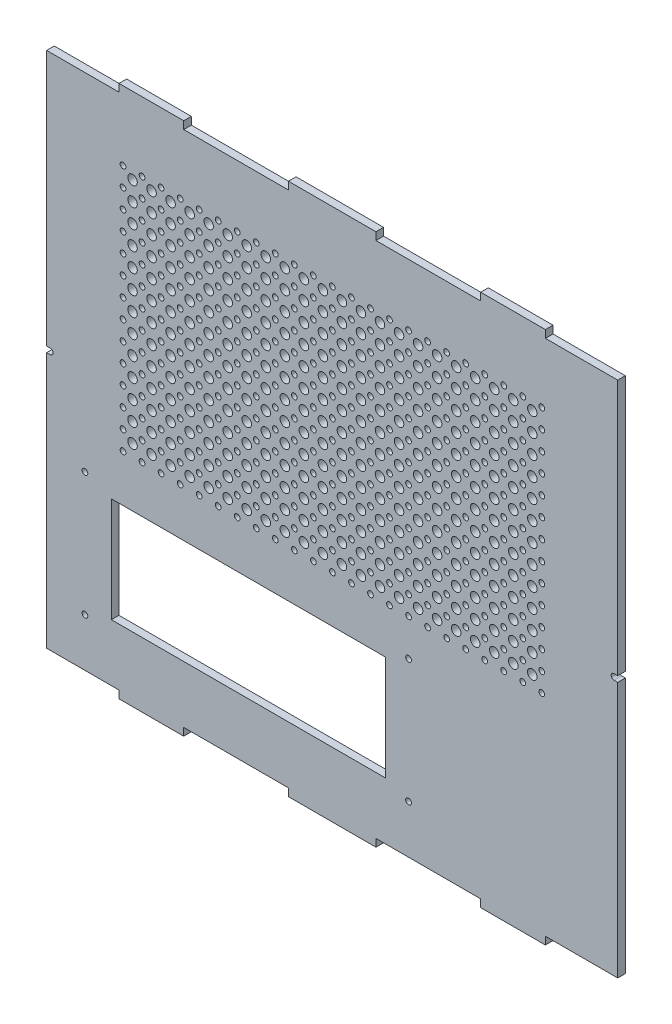
SolidWorks part; units mm, degrees
ref_plane "Front" through (0, 0, 0) normal (0, 0, 1) x (1, 0, 0)
ref_plane "Top" through (0, 0, 0) normal (0, 1, 0) x (1, 0, 0)
ref_plane "Right" through (0, 0, 0) normal (1, 0, 0) x (0, 0, -1)
sketch "Sketch1" plane through (0, 0, 0) normal (0, 0, 1) x (1, 0, 0)
  line L0 (-112, 140) -> (-112, 136)
  line L1 (150, -140) -> (-150, -140)
  line L2 (150, -140) -> (150, 140)
  line L3 (150, 140) -> (-150, 140)
  line L4 (-150, -140) -> (-150, -1.5)
  line L5 (150, -140) -> (-150, 140) construction
  line L6 (150, 140) -> (-150, -140) construction
  line L7 (-78, 136) -> (-78, 140)
  line L8 (-78, 140) -> (-112, 140)
  line L9 (-23, 136) -> (-23, 140)
  line L10 (-23, 140) -> (23, 140)
  line L11 (23, 136) -> (23, 140)
  line L12 (78, 140) -> (112, 140)
  line L13 (78, 136) -> (78, 140)
  line L14 (112, 140) -> (112, 136)
  line L15 (112, 136) -> (-112, 136) construction
  line L16 (-112, 136) -> (112, 136)
  line L17 (-150, 0) -> (150, 0) construction
  line L18 (-112, -136) -> (112, -136)
  line L19 (-78, -140) -> (-112, -140)
  line L20 (-78, -136) -> (-78, -140)
  line L21 (-112, -140) -> (-112, -136)
  line L22 (112, -140) -> (112, -136)
  line L23 (78, -136) -> (78, -140)
  line L24 (78, -140) -> (112, -140)
  line L25 (23, -136) -> (23, -140)
  line L26 (-23, -140) -> (23, -140)
  line L27 (-23, -136) -> (-23, -140)
  line L28 (-150, 136) -> (150, 136)
  line L29 (112, -136) -> (150, -136)
  line L30 (-112, -136) -> (-150, -136)
  line L31 (-150, 0) -> (-148.0495, 0) construction
  line L32 (-150, 1.5) -> (-148.0495, 1.5)
  line L33 (-150, -1.5) -> (-148.0495, -1.5)
  line L34 (-150, 1.5) -> (-150, 140)
  line L35 (0, 0) -> (0, -136) construction
  line L36 (150, 0) -> (148.0495, 0) construction
  line L37 (150, -1.5) -> (148.0495, -1.5)
  line L38 (150, 1.5) -> (148.0495, 1.5)
  line L39 (116.6123, 108.6823) -> (-116.3877, 108.6823) construction
  line L40 (116.6123, 108.6823) -> (116.6123, -35.3177) construction
  line L41 (116.6123, -35.3177) -> (-116.3877, -35.3177) construction
  line L42 (-116.3877, 108.6823) -> (-116.3877, -35.3177) construction
  line L43 (116.6123, 108.6823) -> (-116.3877, -35.3177) construction
  line L44 (116.6123, -35.3177) -> (-116.3877, 108.6823) construction
  line L46 (28, -106) -> (-116, -106)
  line L47 (28, -106) -> (28, -51)
  line L48 (28, -51) -> (-116, -51)
  line L49 (-116, -106) -> (-116, -51)
  line L50 (28, -106) -> (-116, -51) construction
  line L51 (28, -51) -> (-116, -106) construction
  line L52 (-129.8891, -45.6951) -> (40.1123, -45.6951) construction
  line L53 (-129.8891, -45.6951) -> (-129.8891, -110.6262) construction
  line L54 (-129.8891, -110.6262) -> (40.1123, -110.6262) construction
  line L55 (40.1123, -45.6951) -> (40.1123, -110.6262) construction
  line L56 (-44.8884, -110.6262) -> (-44.8884, -45.6951) construction
  line L57 (-129.8891, -78.1607) -> (40.1123, -78.1607) construction
  arc A0 (148.0495, -1.5) -> (148.0495, 1.5) centre (148.0495, 0) cw
  arc A1 (-148.0495, -1.5) -> (-148.0495, 1.5) centre (-148.0495, 0) ccw
  circle A2 centre (-129.8891, -45.6951) radius 1.5
  circle A3 centre (40.1123, -45.6951) radius 1.5
  circle A4 centre (-109.8877, 103.6823) radius 1.5
  circle A5 centre (-99.8877, 103.6823) radius 1.5
  circle A6 centre (-89.8877, 103.6823) radius 1.5
  circle A7 centre (-79.8877, 103.6823) radius 1.5
  circle A8 centre (-69.8877, 103.6823) radius 1.5
  circle A9 centre (-59.8877, 103.6823) radius 1.5
  circle A10 centre (-49.8877, 103.6823) radius 1.5
  circle A11 centre (-39.8877, 103.6823) radius 1.5
  circle A12 centre (-29.8877, 103.6823) radius 1.5
  circle A13 centre (-19.8877, 103.6823) radius 1.5
  circle A14 centre (-9.8877, 103.6823) radius 1.5
  circle A15 centre (0.1123, 103.6823) radius 1.5
  circle A16 centre (10.1123, 103.6823) radius 1.5
  circle A17 centre (20.1123, 103.6823) radius 1.5
  circle A18 centre (30.1123, 103.6823) radius 1.5
  circle A19 centre (40.1123, 103.6823) radius 1.5
  circle A20 centre (50.1123, 103.6823) radius 1.5
  circle A21 centre (60.1123, 103.6823) radius 1.5
  circle A22 centre (70.1123, 103.6823) radius 1.5
  circle A23 centre (80.1123, 103.6823) radius 1.5
  circle A24 centre (90.1123, 103.6823) radius 1.5
  circle A25 centre (100.1123, 103.6823) radius 1.5
  circle A26 centre (110.1123, 103.6823) radius 1.5
  circle A27 centre (-99.8877, 93.6823) radius 1.5
  circle A28 centre (-89.8877, 93.6823) radius 1.5
  circle A29 centre (-79.8877, 93.6823) radius 1.5
  circle A30 centre (-69.8877, 93.6823) radius 1.5
  circle A31 centre (-59.8877, 93.6823) radius 1.5
  circle A32 centre (-49.8877, 93.6823) radius 1.5
  circle A33 centre (-39.8877, 93.6823) radius 1.5
  circle A34 centre (-29.8877, 93.6823) radius 1.5
  circle A35 centre (-19.8877, 93.6823) radius 1.5
  circle A36 centre (-9.8877, 93.6823) radius 1.5
  circle A37 centre (0.1123, 93.6823) radius 1.5
  circle A38 centre (10.1123, 93.6823) radius 1.5
  circle A39 centre (20.1123, 93.6823) radius 1.5
  circle A40 centre (30.1123, 93.6823) radius 1.5
  circle A41 centre (40.1123, 93.6823) radius 1.5
  circle A42 centre (50.1123, 93.6823) radius 1.5
  circle A43 centre (60.1123, 93.6823) radius 1.5
  circle A44 centre (70.1123, 93.6823) radius 1.5
  circle A45 centre (80.1123, 93.6823) radius 1.5
  circle A46 centre (90.1123, 93.6823) radius 1.5
  circle A47 centre (100.1123, 93.6823) radius 1.5
  circle A48 centre (110.1123, 93.6823) radius 1.5
  circle A49 centre (-99.8877, 83.6823) radius 1.5
  circle A50 centre (-89.8877, 83.6823) radius 1.5
  circle A51 centre (-79.8877, 83.6823) radius 1.5
  circle A52 centre (-69.8877, 83.6823) radius 1.5
  circle A53 centre (-59.8877, 83.6823) radius 1.5
  circle A54 centre (-49.8877, 83.6823) radius 1.5
  circle A55 centre (-39.8877, 83.6823) radius 1.5
  circle A56 centre (-29.8877, 83.6823) radius 1.5
  circle A57 centre (-19.8877, 83.6823) radius 1.5
  circle A58 centre (-9.8877, 83.6823) radius 1.5
  circle A59 centre (0.1123, 83.6823) radius 1.5
  circle A60 centre (10.1123, 83.6823) radius 1.5
  circle A61 centre (20.1123, 83.6823) radius 1.5
  circle A62 centre (30.1123, 83.6823) radius 1.5
  circle A63 centre (40.1123, 83.6823) radius 1.5
  circle A64 centre (50.1123, 83.6823) radius 1.5
  circle A65 centre (60.1123, 83.6823) radius 1.5
  circle A66 centre (70.1123, 83.6823) radius 1.5
  circle A67 centre (80.1123, 83.6823) radius 1.5
  circle A68 centre (90.1123, 83.6823) radius 1.5
  circle A69 centre (100.1123, 83.6823) radius 1.5
  circle A70 centre (110.1123, 83.6823) radius 1.5
  circle A71 centre (-99.8877, 73.6823) radius 1.5
  circle A72 centre (-89.8877, 73.6823) radius 1.5
  circle A73 centre (-79.8877, 73.6823) radius 1.5
  circle A74 centre (-69.8877, 73.6823) radius 1.5
  circle A75 centre (-59.8877, 73.6823) radius 1.5
  circle A76 centre (-49.8877, 73.6823) radius 1.5
  circle A77 centre (-39.8877, 73.6823) radius 1.5
  circle A78 centre (-29.8877, 73.6823) radius 1.5
  circle A79 centre (-19.8877, 73.6823) radius 1.5
  circle A80 centre (-9.8877, 73.6823) radius 1.5
  circle A81 centre (0.1123, 73.6823) radius 1.5
  circle A82 centre (10.1123, 73.6823) radius 1.5
  circle A83 centre (20.1123, 73.6823) radius 1.5
  circle A84 centre (30.1123, 73.6823) radius 1.5
  circle A85 centre (40.1123, 73.6823) radius 1.5
  circle A86 centre (50.1123, 73.6823) radius 1.5
  circle A87 centre (60.1123, 73.6823) radius 1.5
  circle A88 centre (70.1123, 73.6823) radius 1.5
  circle A89 centre (80.1123, 73.6823) radius 1.5
  circle A90 centre (90.1123, 73.6823) radius 1.5
  circle A91 centre (100.1123, 73.6823) radius 1.5
  circle A92 centre (110.1123, 73.6823) radius 1.5
  circle A93 centre (-99.8877, 63.6823) radius 1.5
  circle A94 centre (-89.8877, 63.6823) radius 1.5
  circle A95 centre (-79.8877, 63.6823) radius 1.5
  circle A96 centre (-69.8877, 63.6823) radius 1.5
  circle A97 centre (-59.8877, 63.6823) radius 1.5
  circle A98 centre (-49.8877, 63.6823) radius 1.5
  circle A99 centre (-39.8877, 63.6823) radius 1.5
  circle A100 centre (-29.8877, 63.6823) radius 1.5
  circle A101 centre (-19.8877, 63.6823) radius 1.5
  circle A102 centre (-9.8877, 63.6823) radius 1.5
  circle A103 centre (0.1123, 63.6823) radius 1.5
  circle A104 centre (10.1123, 63.6823) radius 1.5
  circle A105 centre (20.1123, 63.6823) radius 1.5
  circle A106 centre (30.1123, 63.6823) radius 1.5
  circle A107 centre (40.1123, 63.6823) radius 1.5
  circle A108 centre (50.1123, 63.6823) radius 1.5
  circle A109 centre (60.1123, 63.6823) radius 1.5
  circle A110 centre (70.1123, 63.6823) radius 1.5
  circle A111 centre (80.1123, 63.6823) radius 1.5
  circle A112 centre (90.1123, 63.6823) radius 1.5
  circle A113 centre (100.1123, 63.6823) radius 1.5
  circle A114 centre (110.1123, 63.6823) radius 1.5
  circle A115 centre (-99.8877, 53.6823) radius 1.5
  circle A116 centre (-89.8877, 53.6823) radius 1.5
  circle A117 centre (-79.8877, 53.6823) radius 1.5
  circle A118 centre (-69.8877, 53.6823) radius 1.5
  circle A119 centre (-59.8877, 53.6823) radius 1.5
  circle A120 centre (-49.8877, 53.6823) radius 1.5
  circle A121 centre (-39.8877, 53.6823) radius 1.5
  circle A122 centre (-29.8877, 53.6823) radius 1.5
  circle A123 centre (-19.8877, 53.6823) radius 1.5
  circle A124 centre (-9.8877, 53.6823) radius 1.5
  circle A125 centre (0.1123, 53.6823) radius 1.5
  circle A126 centre (10.1123, 53.6823) radius 1.5
  circle A127 centre (20.1123, 53.6823) radius 1.5
  circle A128 centre (30.1123, 53.6823) radius 1.5
  circle A129 centre (40.1123, 53.6823) radius 1.5
  circle A130 centre (50.1123, 53.6823) radius 1.5
  circle A131 centre (60.1123, 53.6823) radius 1.5
  circle A132 centre (70.1123, 53.6823) radius 1.5
  circle A133 centre (80.1123, 53.6823) radius 1.5
  circle A134 centre (90.1123, 53.6823) radius 1.5
  circle A135 centre (100.1123, 53.6823) radius 1.5
  circle A136 centre (110.1123, 53.6823) radius 1.5
  circle A137 centre (-99.8877, 43.6823) radius 1.5
  circle A138 centre (-89.8877, 43.6823) radius 1.5
  circle A139 centre (-79.8877, 43.6823) radius 1.5
  circle A140 centre (-69.8877, 43.6823) radius 1.5
  circle A141 centre (-59.8877, 43.6823) radius 1.5
  circle A142 centre (-49.8877, 43.6823) radius 1.5
  circle A143 centre (-39.8877, 43.6823) radius 1.5
  circle A144 centre (-29.8877, 43.6823) radius 1.5
  circle A145 centre (-19.8877, 43.6823) radius 1.5
  circle A146 centre (-9.8877, 43.6823) radius 1.5
  circle A147 centre (0.1123, 43.6823) radius 1.5
  circle A148 centre (10.1123, 43.6823) radius 1.5
  circle A149 centre (20.1123, 43.6823) radius 1.5
  circle A150 centre (30.1123, 43.6823) radius 1.5
  circle A151 centre (40.1123, 43.6823) radius 1.5
  circle A152 centre (50.1123, 43.6823) radius 1.5
  circle A153 centre (60.1123, 43.6823) radius 1.5
  circle A154 centre (70.1123, 43.6823) radius 1.5
  circle A155 centre (80.1123, 43.6823) radius 1.5
  circle A156 centre (90.1123, 43.6823) radius 1.5
  circle A157 centre (100.1123, 43.6823) radius 1.5
  circle A158 centre (110.1123, 43.6823) radius 1.5
  circle A159 centre (-99.8877, 33.6823) radius 1.5
  circle A160 centre (-89.8877, 33.6823) radius 1.5
  circle A161 centre (-79.8877, 33.6823) radius 1.5
  circle A162 centre (-69.8877, 33.6823) radius 1.5
  circle A163 centre (-59.8877, 33.6823) radius 1.5
  circle A164 centre (-49.8877, 33.6823) radius 1.5
  circle A165 centre (-39.8877, 33.6823) radius 1.5
  circle A166 centre (-29.8877, 33.6823) radius 1.5
  circle A167 centre (-19.8877, 33.6823) radius 1.5
  circle A168 centre (-9.8877, 33.6823) radius 1.5
  circle A169 centre (0.1123, 33.6823) radius 1.5
  circle A170 centre (10.1123, 33.6823) radius 1.5
  circle A171 centre (20.1123, 33.6823) radius 1.5
  circle A172 centre (30.1123, 33.6823) radius 1.5
  circle A173 centre (40.1123, 33.6823) radius 1.5
  circle A174 centre (50.1123, 33.6823) radius 1.5
  circle A175 centre (60.1123, 33.6823) radius 1.5
  circle A176 centre (70.1123, 33.6823) radius 1.5
  circle A177 centre (80.1123, 33.6823) radius 1.5
  circle A178 centre (90.1123, 33.6823) radius 1.5
  circle A179 centre (100.1123, 33.6823) radius 1.5
  circle A180 centre (110.1123, 33.6823) radius 1.5
  circle A181 centre (-99.8877, 23.6823) radius 1.5
  circle A182 centre (-89.8877, 23.6823) radius 1.5
  circle A183 centre (-79.8877, 23.6823) radius 1.5
  circle A184 centre (-69.8877, 23.6823) radius 1.5
  circle A185 centre (-59.8877, 23.6823) radius 1.5
  circle A186 centre (-49.8877, 23.6823) radius 1.5
  circle A187 centre (-39.8877, 23.6823) radius 1.5
  circle A188 centre (-29.8877, 23.6823) radius 1.5
  circle A189 centre (-19.8877, 23.6823) radius 1.5
  circle A190 centre (-9.8877, 23.6823) radius 1.5
  circle A191 centre (0.1123, 23.6823) radius 1.5
  circle A192 centre (10.1123, 23.6823) radius 1.5
  circle A193 centre (20.1123, 23.6823) radius 1.5
  circle A194 centre (30.1123, 23.6823) radius 1.5
  circle A195 centre (40.1123, 23.6823) radius 1.5
  circle A196 centre (50.1123, 23.6823) radius 1.5
  circle A197 centre (60.1123, 23.6823) radius 1.5
  circle A198 centre (70.1123, 23.6823) radius 1.5
  circle A199 centre (80.1123, 23.6823) radius 1.5
  circle A200 centre (90.1123, 23.6823) radius 1.5
  circle A201 centre (100.1123, 23.6823) radius 1.5
  circle A202 centre (110.1123, 23.6823) radius 1.5
  circle A203 centre (-99.8877, 13.6823) radius 1.5
  circle A204 centre (-89.8877, 13.6823) radius 1.5
  circle A205 centre (-79.8877, 13.6823) radius 1.5
  circle A206 centre (-69.8877, 13.6823) radius 1.5
  circle A207 centre (-59.8877, 13.6823) radius 1.5
  circle A208 centre (-49.8877, 13.6823) radius 1.5
  circle A209 centre (-39.8877, 13.6823) radius 1.5
  circle A210 centre (-29.8877, 13.6823) radius 1.5
  circle A211 centre (-19.8877, 13.6823) radius 1.5
  circle A212 centre (-9.8877, 13.6823) radius 1.5
  circle A213 centre (0.1123, 13.6823) radius 1.5
  circle A214 centre (10.1123, 13.6823) radius 1.5
  circle A215 centre (20.1123, 13.6823) radius 1.5
  circle A216 centre (30.1123, 13.6823) radius 1.5
  circle A217 centre (40.1123, 13.6823) radius 1.5
  circle A218 centre (50.1123, 13.6823) radius 1.5
  circle A219 centre (60.1123, 13.6823) radius 1.5
  circle A220 centre (70.1123, 13.6823) radius 1.5
  circle A221 centre (80.1123, 13.6823) radius 1.5
  circle A222 centre (90.1123, 13.6823) radius 1.5
  circle A223 centre (100.1123, 13.6823) radius 1.5
  circle A224 centre (110.1123, 13.6823) radius 1.5
  circle A225 centre (-99.8877, 3.6823) radius 1.5
  circle A226 centre (-89.8877, 3.6823) radius 1.5
  circle A227 centre (-79.8877, 3.6823) radius 1.5
  circle A228 centre (-69.8877, 3.6823) radius 1.5
  circle A229 centre (-59.8877, 3.6823) radius 1.5
  circle A230 centre (-49.8877, 3.6823) radius 1.5
  circle A231 centre (-39.8877, 3.6823) radius 1.5
  circle A232 centre (-29.8877, 3.6823) radius 1.5
  circle A233 centre (-19.8877, 3.6823) radius 1.5
  circle A234 centre (-9.8877, 3.6823) radius 1.5
  circle A235 centre (0.1123, 3.6823) radius 1.5
  circle A236 centre (10.1123, 3.6823) radius 1.5
  circle A237 centre (20.1123, 3.6823) radius 1.5
  circle A238 centre (30.1123, 3.6823) radius 1.5
  circle A239 centre (40.1123, 3.6823) radius 1.5
  circle A240 centre (50.1123, 3.6823) radius 1.5
  circle A241 centre (60.1123, 3.6823) radius 1.5
  circle A242 centre (70.1123, 3.6823) radius 1.5
  circle A243 centre (80.1123, 3.6823) radius 1.5
  circle A244 centre (90.1123, 3.6823) radius 1.5
  circle A245 centre (100.1123, 3.6823) radius 1.5
  circle A246 centre (110.1123, 3.6823) radius 1.5
  circle A247 centre (-99.8877, -6.3177) radius 1.5
  circle A248 centre (-89.8877, -6.3177) radius 1.5
  circle A249 centre (-79.8877, -6.3177) radius 1.5
  circle A250 centre (-69.8877, -6.3177) radius 1.5
  circle A251 centre (-59.8877, -6.3177) radius 1.5
  circle A252 centre (-49.8877, -6.3177) radius 1.5
  circle A253 centre (-39.8877, -6.3177) radius 1.5
  circle A254 centre (-29.8877, -6.3177) radius 1.5
  circle A255 centre (-19.8877, -6.3177) radius 1.5
  circle A256 centre (-9.8877, -6.3177) radius 1.5
  circle A257 centre (0.1123, -6.3177) radius 1.5
  circle A258 centre (10.1123, -6.3177) radius 1.5
  circle A259 centre (20.1123, -6.3177) radius 1.5
  circle A260 centre (30.1123, -6.3177) radius 1.5
  circle A261 centre (40.1123, -6.3177) radius 1.5
  circle A262 centre (50.1123, -6.3177) radius 1.5
  circle A263 centre (60.1123, -6.3177) radius 1.5
  circle A264 centre (70.1123, -6.3177) radius 1.5
  circle A265 centre (80.1123, -6.3177) radius 1.5
  circle A266 centre (90.1123, -6.3177) radius 1.5
  circle A267 centre (100.1123, -6.3177) radius 1.5
  circle A268 centre (110.1123, -6.3177) radius 1.5
  circle A269 centre (-99.8877, -16.3177) radius 1.5
  circle A270 centre (-89.8877, -16.3177) radius 1.5
  circle A271 centre (-79.8877, -16.3177) radius 1.5
  circle A272 centre (-69.8877, -16.3177) radius 1.5
  circle A273 centre (-59.8877, -16.3177) radius 1.5
  circle A274 centre (-49.8877, -16.3177) radius 1.5
  circle A275 centre (-39.8877, -16.3177) radius 1.5
  circle A276 centre (-29.8877, -16.3177) radius 1.5
  circle A277 centre (-19.8877, -16.3177) radius 1.5
  circle A278 centre (-9.8877, -16.3177) radius 1.5
  circle A279 centre (0.1123, -16.3177) radius 1.5
  circle A280 centre (10.1123, -16.3177) radius 1.5
  circle A281 centre (20.1123, -16.3177) radius 1.5
  circle A282 centre (30.1123, -16.3177) radius 1.5
  circle A283 centre (40.1123, -16.3177) radius 1.5
  circle A284 centre (50.1123, -16.3177) radius 1.5
  circle A285 centre (60.1123, -16.3177) radius 1.5
  circle A286 centre (70.1123, -16.3177) radius 1.5
  circle A287 centre (80.1123, -16.3177) radius 1.5
  circle A288 centre (90.1123, -16.3177) radius 1.5
  circle A289 centre (100.1123, -16.3177) radius 1.5
  circle A290 centre (110.1123, -16.3177) radius 1.5
  circle A291 centre (-99.8877, -26.3177) radius 1.5
  circle A292 centre (-89.8877, -26.3177) radius 1.5
  circle A293 centre (-79.8877, -26.3177) radius 1.5
  circle A294 centre (-69.8877, -26.3177) radius 1.5
  circle A295 centre (-59.8877, -26.3177) radius 1.5
  circle A296 centre (-49.8877, -26.3177) radius 1.5
  circle A297 centre (-39.8877, -26.3177) radius 1.5
  circle A298 centre (-29.8877, -26.3177) radius 1.5
  circle A299 centre (-19.8877, -26.3177) radius 1.5
  circle A300 centre (-9.8877, -26.3177) radius 1.5
  circle A301 centre (0.1123, -26.3177) radius 1.5
  circle A302 centre (10.1123, -26.3177) radius 1.5
  circle A303 centre (20.1123, -26.3177) radius 1.5
  circle A304 centre (30.1123, -26.3177) radius 1.5
  circle A305 centre (40.1123, -26.3177) radius 1.5
  circle A306 centre (50.1123, -26.3177) radius 1.5
  circle A307 centre (60.1123, -26.3177) radius 1.5
  circle A308 centre (70.1123, -26.3177) radius 1.5
  circle A309 centre (80.1123, -26.3177) radius 1.5
  circle A310 centre (90.1123, -26.3177) radius 1.5
  circle A311 centre (100.1123, -26.3177) radius 1.5
  circle A312 centre (110.1123, -26.3177) radius 1.5
  circle A313 centre (-109.8877, 93.6823) radius 1.5
  circle A314 centre (-109.8877, 83.6823) radius 1.5
  circle A315 centre (-109.8877, 73.6823) radius 1.5
  circle A316 centre (-109.8877, 63.6823) radius 1.5
  circle A317 centre (-109.8877, 53.6823) radius 1.5
  circle A318 centre (-109.8877, 43.6823) radius 1.5
  circle A319 centre (-109.8877, 33.6823) radius 1.5
  circle A320 centre (-109.8877, 23.6823) radius 1.5
  circle A321 centre (-109.8877, 13.6823) radius 1.5
  circle A322 centre (-109.8877, 3.6823) radius 1.5
  circle A323 centre (-109.8877, -6.3177) radius 1.5
  circle A324 centre (-109.8877, -16.3177) radius 1.5
  circle A325 centre (-109.8877, -26.3177) radius 1.5
  circle A326 centre (-94.8877, 99.6823) radius 2.5
  circle A327 centre (-84.8877, 99.6823) radius 2.5
  circle A328 centre (-74.8877, 99.6823) radius 2.5
  circle A329 centre (-64.8877, 99.6823) radius 2.5
  circle A330 centre (-54.8877, 99.6823) radius 2.5
  circle A331 centre (-44.8877, 99.6823) radius 2.5
  circle A332 centre (-34.8877, 99.6823) radius 2.5
  circle A333 centre (-24.8877, 99.6823) radius 2.5
  circle A334 centre (-14.8877, 99.6823) radius 2.5
  circle A335 centre (-4.8877, 99.6823) radius 2.5
  circle A336 centre (5.1123, 99.6823) radius 2.5
  circle A337 centre (15.1123, 99.6823) radius 2.5
  circle A338 centre (25.1123, 99.6823) radius 2.5
  circle A339 centre (35.1123, 99.6823) radius 2.5
  circle A340 centre (45.1123, 99.6823) radius 2.5
  circle A341 centre (55.1123, 99.6823) radius 2.5
  circle A342 centre (65.1123, 99.6823) radius 2.5
  circle A343 centre (75.1123, 99.6823) radius 2.5
  circle A344 centre (85.1123, 99.6823) radius 2.5
  circle A345 centre (95.1123, 99.6823) radius 2.5
  circle A346 centre (105.1123, 99.6823) radius 2.5
  circle A347 centre (-94.8877, 89.6823) radius 2.5
  circle A348 centre (-84.8877, 89.6823) radius 2.5
  circle A349 centre (-74.8877, 89.6823) radius 2.5
  circle A350 centre (-64.8877, 89.6823) radius 2.5
  circle A351 centre (-54.8877, 89.6823) radius 2.5
  circle A352 centre (-44.8877, 89.6823) radius 2.5
  circle A353 centre (-34.8877, 89.6823) radius 2.5
  circle A354 centre (-24.8877, 89.6823) radius 2.5
  circle A355 centre (-14.8877, 89.6823) radius 2.5
  circle A356 centre (-4.8877, 89.6823) radius 2.5
  circle A357 centre (5.1123, 89.6823) radius 2.5
  circle A358 centre (15.1123, 89.6823) radius 2.5
  circle A359 centre (25.1123, 89.6823) radius 2.5
  circle A360 centre (35.1123, 89.6823) radius 2.5
  circle A361 centre (45.1123, 89.6823) radius 2.5
  circle A362 centre (55.1123, 89.6823) radius 2.5
  circle A363 centre (65.1123, 89.6823) radius 2.5
  circle A364 centre (75.1123, 89.6823) radius 2.5
  circle A365 centre (85.1123, 89.6823) radius 2.5
  circle A366 centre (95.1123, 89.6823) radius 2.5
  circle A367 centre (105.1123, 89.6823) radius 2.5
  circle A368 centre (-94.8877, 79.6823) radius 2.5
  circle A369 centre (-84.8877, 79.6823) radius 2.5
  circle A370 centre (-74.8877, 79.6823) radius 2.5
  circle A371 centre (-64.8877, 79.6823) radius 2.5
  circle A372 centre (-54.8877, 79.6823) radius 2.5
  circle A373 centre (-44.8877, 79.6823) radius 2.5
  circle A374 centre (-34.8877, 79.6823) radius 2.5
  circle A375 centre (-24.8877, 79.6823) radius 2.5
  circle A376 centre (-14.8877, 79.6823) radius 2.5
  circle A377 centre (-4.8877, 79.6823) radius 2.5
  circle A378 centre (5.1123, 79.6823) radius 2.5
  circle A379 centre (15.1123, 79.6823) radius 2.5
  circle A380 centre (25.1123, 79.6823) radius 2.5
  circle A381 centre (35.1123, 79.6823) radius 2.5
  circle A382 centre (45.1123, 79.6823) radius 2.5
  circle A383 centre (55.1123, 79.6823) radius 2.5
  circle A384 centre (65.1123, 79.6823) radius 2.5
  circle A385 centre (75.1123, 79.6823) radius 2.5
  circle A386 centre (85.1123, 79.6823) radius 2.5
  circle A387 centre (95.1123, 79.6823) radius 2.5
  circle A388 centre (105.1123, 79.6823) radius 2.5
  circle A389 centre (-94.8877, 69.6823) radius 2.5
  circle A390 centre (-84.8877, 69.6823) radius 2.5
  circle A391 centre (-74.8877, 69.6823) radius 2.5
  circle A392 centre (-64.8877, 69.6823) radius 2.5
  circle A393 centre (-54.8877, 69.6823) radius 2.5
  circle A394 centre (-44.8877, 69.6823) radius 2.5
  circle A395 centre (-34.8877, 69.6823) radius 2.5
  circle A396 centre (-24.8877, 69.6823) radius 2.5
  circle A397 centre (-14.8877, 69.6823) radius 2.5
  circle A398 centre (-4.8877, 69.6823) radius 2.5
  circle A399 centre (5.1123, 69.6823) radius 2.5
  circle A400 centre (15.1123, 69.6823) radius 2.5
  circle A401 centre (25.1123, 69.6823) radius 2.5
  circle A402 centre (35.1123, 69.6823) radius 2.5
  circle A403 centre (45.1123, 69.6823) radius 2.5
  circle A404 centre (55.1123, 69.6823) radius 2.5
  circle A405 centre (65.1123, 69.6823) radius 2.5
  circle A406 centre (75.1123, 69.6823) radius 2.5
  circle A407 centre (85.1123, 69.6823) radius 2.5
  circle A408 centre (95.1123, 69.6823) radius 2.5
  circle A409 centre (105.1123, 69.6823) radius 2.5
  circle A410 centre (-94.8877, 59.6823) radius 2.5
  circle A411 centre (-84.8877, 59.6823) radius 2.5
  circle A412 centre (-74.8877, 59.6823) radius 2.5
  circle A413 centre (-64.8877, 59.6823) radius 2.5
  circle A414 centre (-54.8877, 59.6823) radius 2.5
  circle A415 centre (-44.8877, 59.6823) radius 2.5
  circle A416 centre (-34.8877, 59.6823) radius 2.5
  circle A417 centre (-24.8877, 59.6823) radius 2.5
  circle A418 centre (-104.8877, 99.6823) radius 2.5
  circle A419 centre (-14.8877, 59.6823) radius 2.5
  circle A420 centre (-4.8877, 59.6823) radius 2.5
  circle A421 centre (5.1123, 59.6823) radius 2.5
  circle A422 centre (15.1123, 59.6823) radius 2.5
  circle A423 centre (25.1123, 59.6823) radius 2.5
  circle A424 centre (35.1123, 59.6823) radius 2.5
  circle A425 centre (45.1123, 59.6823) radius 2.5
  circle A426 centre (55.1123, 59.6823) radius 2.5
  circle A427 centre (65.1123, 59.6823) radius 2.5
  circle A428 centre (75.1123, 59.6823) radius 2.5
  circle A429 centre (85.1123, 59.6823) radius 2.5
  circle A430 centre (95.1123, 59.6823) radius 2.5
  circle A431 centre (105.1123, 59.6823) radius 2.5
  circle A432 centre (-94.8877, 49.6823) radius 2.5
  circle A433 centre (-84.8877, 49.6823) radius 2.5
  circle A434 centre (-74.8877, 49.6823) radius 2.5
  circle A435 centre (-64.8877, 49.6823) radius 2.5
  circle A436 centre (-54.8877, 49.6823) radius 2.5
  circle A437 centre (-44.8877, 49.6823) radius 2.5
  circle A438 centre (-34.8877, 49.6823) radius 2.5
  circle A439 centre (-24.8877, 49.6823) radius 2.5
  circle A440 centre (-14.8877, 49.6823) radius 2.5
  circle A441 centre (-4.8877, 49.6823) radius 2.5
  circle A442 centre (5.1123, 49.6823) radius 2.5
  circle A443 centre (15.1123, 49.6823) radius 2.5
  circle A444 centre (25.1123, 49.6823) radius 2.5
  circle A445 centre (35.1123, 49.6823) radius 2.5
  circle A446 centre (45.1123, 49.6823) radius 2.5
  circle A447 centre (55.1123, 49.6823) radius 2.5
  circle A448 centre (65.1123, 49.6823) radius 2.5
  circle A449 centre (75.1123, 49.6823) radius 2.5
  circle A450 centre (85.1123, 49.6823) radius 2.5
  circle A451 centre (95.1123, 49.6823) radius 2.5
  circle A452 centre (105.1123, 49.6823) radius 2.5
  circle A453 centre (-94.8877, 39.6823) radius 2.5
  circle A454 centre (-84.8877, 39.6823) radius 2.5
  circle A455 centre (-74.8877, 39.6823) radius 2.5
  circle A456 centre (-64.8877, 39.6823) radius 2.5
  circle A457 centre (-54.8877, 39.6823) radius 2.5
  circle A458 centre (-44.8877, 39.6823) radius 2.5
  circle A459 centre (-34.8877, 39.6823) radius 2.5
  circle A460 centre (-24.8877, 39.6823) radius 2.5
  circle A461 centre (-14.8877, 39.6823) radius 2.5
  circle A462 centre (-4.8877, 39.6823) radius 2.5
  circle A463 centre (5.1123, 39.6823) radius 2.5
  circle A464 centre (15.1123, 39.6823) radius 2.5
  circle A465 centre (25.1123, 39.6823) radius 2.5
  circle A466 centre (35.1123, 39.6823) radius 2.5
  circle A467 centre (45.1123, 39.6823) radius 2.5
  circle A468 centre (55.1123, 39.6823) radius 2.5
  circle A469 centre (65.1123, 39.6823) radius 2.5
  circle A470 centre (75.1123, 39.6823) radius 2.5
  circle A471 centre (85.1123, 39.6823) radius 2.5
  circle A472 centre (95.1123, 39.6823) radius 2.5
  circle A473 centre (105.1123, 39.6823) radius 2.5
  circle A474 centre (-94.8877, 29.6823) radius 2.5
  circle A475 centre (-84.8877, 29.6823) radius 2.5
  circle A476 centre (-74.8877, 29.6823) radius 2.5
  circle A477 centre (-64.8877, 29.6823) radius 2.5
  circle A478 centre (-54.8877, 29.6823) radius 2.5
  circle A479 centre (-44.8877, 29.6823) radius 2.5
  circle A480 centre (-34.8877, 29.6823) radius 2.5
  circle A481 centre (-24.8877, 29.6823) radius 2.5
  circle A482 centre (-14.8877, 29.6823) radius 2.5
  circle A483 centre (-4.8877, 29.6823) radius 2.5
  circle A484 centre (5.1123, 29.6823) radius 2.5
  circle A485 centre (15.1123, 29.6823) radius 2.5
  circle A486 centre (25.1123, 29.6823) radius 2.5
  circle A487 centre (35.1123, 29.6823) radius 2.5
  circle A488 centre (45.1123, 29.6823) radius 2.5
  circle A489 centre (55.1123, 29.6823) radius 2.5
  circle A490 centre (65.1123, 29.6823) radius 2.5
  circle A491 centre (75.1123, 29.6823) radius 2.5
  circle A492 centre (85.1123, 29.6823) radius 2.5
  circle A493 centre (95.1123, 29.6823) radius 2.5
  circle A494 centre (105.1123, 29.6823) radius 2.5
  circle A495 centre (-94.8877, 19.6823) radius 2.5
  circle A496 centre (-84.8877, 19.6823) radius 2.5
  circle A497 centre (-74.8877, 19.6823) radius 2.5
  circle A498 centre (-64.8877, 19.6823) radius 2.5
  circle A499 centre (-54.8877, 19.6823) radius 2.5
  circle A500 centre (-44.8877, 19.6823) radius 2.5
  circle A501 centre (-34.8877, 19.6823) radius 2.5
  circle A502 centre (-24.8877, 19.6823) radius 2.5
  circle A503 centre (-14.8877, 19.6823) radius 2.5
  circle A504 centre (-4.8877, 19.6823) radius 2.5
  circle A505 centre (5.1123, 19.6823) radius 2.5
  circle A506 centre (15.1123, 19.6823) radius 2.5
  circle A507 centre (25.1123, 19.6823) radius 2.5
  circle A508 centre (35.1123, 19.6823) radius 2.5
  circle A509 centre (45.1123, 19.6823) radius 2.5
  circle A510 centre (55.1123, 19.6823) radius 2.5
  circle A511 centre (65.1123, 19.6823) radius 2.5
  circle A512 centre (75.1123, 19.6823) radius 2.5
  circle A513 centre (85.1123, 19.6823) radius 2.5
  circle A514 centre (95.1123, 19.6823) radius 2.5
  circle A515 centre (105.1123, 19.6823) radius 2.5
  circle A516 centre (-94.8877, 9.6823) radius 2.5
  circle A517 centre (-84.8877, 9.6823) radius 2.5
  circle A518 centre (-74.8877, 9.6823) radius 2.5
  circle A519 centre (-64.8877, 9.6823) radius 2.5
  circle A520 centre (-54.8877, 9.6823) radius 2.5
  circle A521 centre (-44.8877, 9.6823) radius 2.5
  circle A522 centre (-34.8877, 9.6823) radius 2.5
  circle A523 centre (-24.8877, 9.6823) radius 2.5
  circle A524 centre (-14.8877, 9.6823) radius 2.5
  circle A525 centre (-4.8877, 9.6823) radius 2.5
  circle A526 centre (5.1123, 9.6823) radius 2.5
  circle A527 centre (15.1123, 9.6823) radius 2.5
  circle A528 centre (25.1123, 9.6823) radius 2.5
  circle A529 centre (35.1123, 9.6823) radius 2.5
  circle A530 centre (45.1123, 9.6823) radius 2.5
  circle A531 centre (55.1123, 9.6823) radius 2.5
  circle A532 centre (65.1123, 9.6823) radius 2.5
  circle A533 centre (75.1123, 9.6823) radius 2.5
  circle A534 centre (85.1123, 9.6823) radius 2.5
  circle A535 centre (95.1123, 9.6823) radius 2.5
  circle A536 centre (105.1123, 9.6823) radius 2.5
  circle A537 centre (-94.8877, -0.3177) radius 2.5
  circle A538 centre (-84.8877, -0.3177) radius 2.5
  circle A539 centre (-74.8877, -0.3177) radius 2.5
  circle A540 centre (-64.8877, -0.3177) radius 2.5
  circle A541 centre (-54.8877, -0.3177) radius 2.5
  circle A542 centre (-44.8877, -0.3177) radius 2.5
  circle A543 centre (-34.8877, -0.3177) radius 2.5
  circle A544 centre (-24.8877, -0.3177) radius 2.5
  circle A545 centre (-14.8877, -0.3177) radius 2.5
  circle A546 centre (-4.8877, -0.3177) radius 2.5
  circle A547 centre (5.1123, -0.3177) radius 2.5
  circle A548 centre (15.1123, -0.3177) radius 2.5
  circle A549 centre (25.1123, -0.3177) radius 2.5
  circle A550 centre (35.1123, -0.3177) radius 2.5
  circle A551 centre (45.1123, -0.3177) radius 2.5
  circle A552 centre (55.1123, -0.3177) radius 2.5
  circle A553 centre (65.1123, -0.3177) radius 2.5
  circle A554 centre (75.1123, -0.3177) radius 2.5
  circle A555 centre (85.1123, -0.3177) radius 2.5
  circle A556 centre (95.1123, -0.3177) radius 2.5
  circle A557 centre (105.1123, -0.3177) radius 2.5
  circle A558 centre (-94.8877, -10.3177) radius 2.5
  circle A559 centre (-84.8877, -10.3177) radius 2.5
  circle A560 centre (-74.8877, -10.3177) radius 2.5
  circle A561 centre (-64.8877, -10.3177) radius 2.5
  circle A562 centre (-54.8877, -10.3177) radius 2.5
  circle A563 centre (-44.8877, -10.3177) radius 2.5
  circle A564 centre (-34.8877, -10.3177) radius 2.5
  circle A565 centre (-24.8877, -10.3177) radius 2.5
  circle A566 centre (-14.8877, -10.3177) radius 2.5
  circle A567 centre (-4.8877, -10.3177) radius 2.5
  circle A568 centre (5.1123, -10.3177) radius 2.5
  circle A569 centre (15.1123, -10.3177) radius 2.5
  circle A570 centre (25.1123, -10.3177) radius 2.5
  circle A571 centre (35.1123, -10.3177) radius 2.5
  circle A572 centre (45.1123, -10.3177) radius 2.5
  circle A573 centre (55.1123, -10.3177) radius 2.5
  circle A574 centre (65.1123, -10.3177) radius 2.5
  circle A575 centre (75.1123, -10.3177) radius 2.5
  circle A576 centre (85.1123, -10.3177) radius 2.5
  circle A577 centre (95.1123, -10.3177) radius 2.5
  circle A578 centre (105.1123, -10.3177) radius 2.5
  circle A579 centre (-94.8877, -20.3177) radius 2.5
  circle A580 centre (-84.8877, -20.3177) radius 2.5
  circle A581 centre (-74.8877, -20.3177) radius 2.5
  circle A582 centre (-64.8877, -20.3177) radius 2.5
  circle A583 centre (-54.8877, -20.3177) radius 2.5
  circle A584 centre (-44.8877, -20.3177) radius 2.5
  circle A585 centre (-34.8877, -20.3177) radius 2.5
  circle A586 centre (-24.8877, -20.3177) radius 2.5
  circle A587 centre (-14.8877, -20.3177) radius 2.5
  circle A588 centre (-4.8877, -20.3177) radius 2.5
  circle A589 centre (5.1123, -20.3177) radius 2.5
  circle A590 centre (15.1123, -20.3177) radius 2.5
  circle A591 centre (25.1123, -20.3177) radius 2.5
  circle A592 centre (35.1123, -20.3177) radius 2.5
  circle A593 centre (45.1123, -20.3177) radius 2.5
  circle A594 centre (55.1123, -20.3177) radius 2.5
  circle A595 centre (65.1123, -20.3177) radius 2.5
  circle A596 centre (75.1123, -20.3177) radius 2.5
  circle A597 centre (85.1123, -20.3177) radius 2.5
  circle A598 centre (95.1123, -20.3177) radius 2.5
  circle A599 centre (105.1123, -20.3177) radius 2.5
  circle A600 centre (-104.8877, 89.6823) radius 2.5
  circle A601 centre (-104.8877, 79.6823) radius 2.5
  circle A602 centre (-104.8877, 69.6823) radius 2.5
  circle A603 centre (-104.8877, 59.6823) radius 2.5
  circle A604 centre (-104.8877, 49.6823) radius 2.5
  circle A605 centre (-104.8877, 39.6823) radius 2.5
  circle A606 centre (-104.8877, 29.6823) radius 2.5
  circle A607 centre (-104.8877, 19.6823) radius 2.5
  circle A608 centre (-104.8877, 9.6823) radius 2.5
  circle A609 centre (-104.8877, -0.3177) radius 2.5
  circle A610 centre (-104.8877, -10.3177) radius 2.5
  circle A611 centre (-104.8877, -20.3177) radius 2.5
  circle A612 centre (40.1123, -110.6262) radius 1.5
  circle A613 centre (-129.8891, -110.6262) radius 1.5
  point P0 (0, 0)
  point P12 (-42.1724, 135.5053)
  point P15 (0, 140)
  point P20 (58.8276, 135.5053)
  point P35 (0, -140)
  point P40 (-149.0247, 0)
  point P53 (149.0247, 0)
  point P54 (0.1123, 36.6823)
  point P55 (-44, -78.5)
  point P1444 (-44.8884, -78.1607)
  dimension "D12" = 144
  dimension "D14" = 3
  dimension "D20" = 3
  dimension "D1" = 300
  dimension "D2" = 280
  dimension "D3" = 34
  dimension "D4" = 46
  dimension "D5" = 4
  dimension "D6" = 55
  dimension "D7" = 55
  dimension "D8" = 34
  dimension "D9" = 38
  dimension "D10" = 1.5
  dimension "D11" = 0.9753
  dimension "D13" = 233
  dimension "D15" = 6.5
  dimension "D16" = 11.5
  dimension "D17" = 55
  dimension "D18" = 34
  dimension "D19" = 34
extrude "Boss-Extrude1" add sketch "Sketch1" along normal blind 4 contours L0 L16 L7 L3 | L9 L16 L11 L3 | L13 L16 L14 L3 | L21 L1 L20 L18 | L18 L27 L1 L25 | L18 L23 L1 L22 | L30 L18 L29 L2 L28 L16 L4 region at (-95, 138, 0) region at (5.3066, 4.7618, 0) region at (0, 138, 0) region at (95, 138, 0) region at (-95, -138, 0) region at (0, -138, 0) region at (95, -138, 0)
